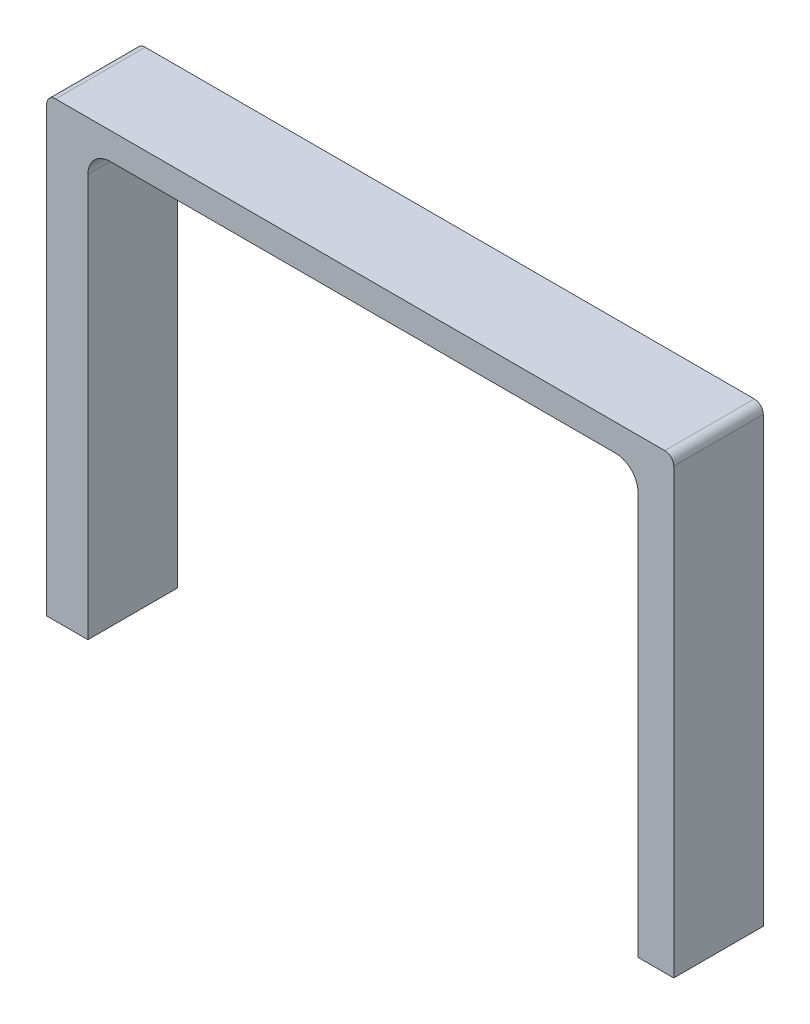
SolidWorks part; units mm, degrees
ref_plane "Front" through (0, 0, 0) normal (0, 0, 1) x (1, 0, 0)
ref_plane "Top" through (0, 0, 0) normal (0, 1, 0) x (1, 0, 0)
ref_plane "Right" through (0, 0, 0) normal (1, 0, 0) x (0, 0, -1)
sketch "Sketch1" plane through (0, 0, 0) normal (0, 0, 1) x (1, 0, 0)
  line L0 (78.7654, -64.135) -> (88.9254, -64.135)
  line L1 (-88.9254, 64.135) -> (88.9254, 64.135)
  line L2 (-88.9254, 64.135) -> (-88.9254, -64.135)
  line L3 (-88.9254, -64.135) -> (-77.2414, -64.135)
  line L4 (88.9254, 64.135) -> (88.9254, -64.135)
  line L5 (-88.9254, 64.135) -> (88.9254, -64.135) construction
  line L6 (-88.9254, -64.135) -> (88.9254, 64.135) construction
  line L7 (78.7654, 56.515) -> (-77.2414, 56.515)
  line L8 (78.7654, 56.515) -> (78.7654, -64.135)
  line L10 (-77.2414, 56.515) -> (-77.2414, -64.135)
  point P0 (0, 0)
  point P10 (-79.4387, 23.5806)
  dimension "D1" = 11.684
  dimension "D2" = 156.0068
  dimension "D3" = 7.62
  dimension "D4" = 10.16
  dimension "D5" = 128.27
extrude "Boss-Extrude1" add sketch "Sketch1" along normal blind 25.4
fillet "Fillet1" radius 6.35 2 edges at (-77.2414, 56.515, 12.7) (78.7654, 56.515, 12.7)
fillet "Fillet2" radius 2.54 2 edges at (-88.9254, 64.135, 12.7) (88.9254, 64.135, 12.7)
